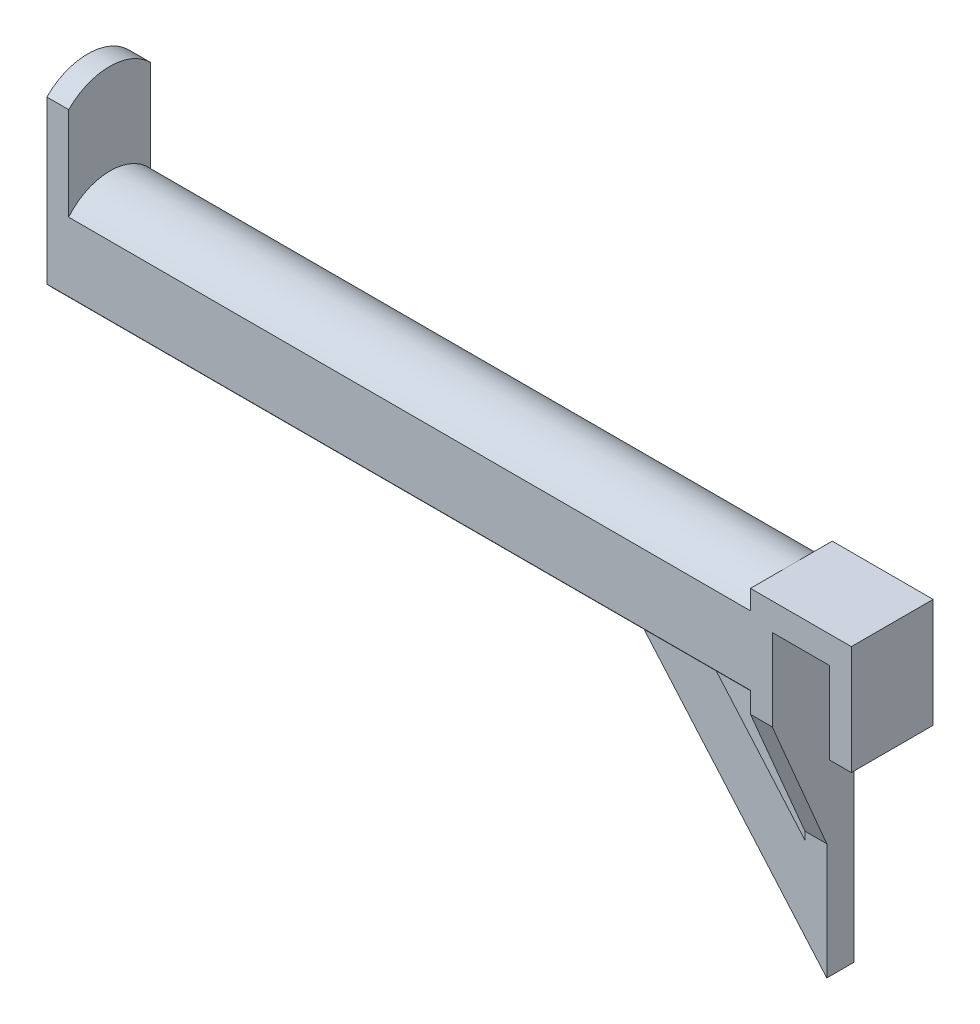
SolidWorks part; units mm, degrees
ref_plane "Front Plane" through (0, 0, 0) normal (0, 0, 1) x (1, 0, 0)
ref_plane "Top Plane" through (0, 0, 0) normal (0, 1, 0) x (1, 0, 0)
ref_plane "Right Plane" through (0, 0, 0) normal (1, 0, 0) x (0, 0, -1)
sketch "Sketch1" plane through (0, 0, 0) normal (0, 0, 1) x (1, 0, 0)
  line L0 (0, 0) -> (21, 0)
  line L1 (21, 0) -> (21, -30)
  line L2 (21, -30) -> (29, -30)
  line L3 (29, -30) -> (29, 10)
  line L4 (29, 10) -> (-8, 10)
  line L5 (-8, 10) -> (-8, -30)
  line L6 (-8, -30) -> (0, -30)
  line L7 (0, -30) -> (0, 0)
  line L8 (0, -30) -> (21, -30) construction
  dimension "D1" = 8
  dimension "D2" = 21
  dimension "D3" = 10
  dimension "D4" = 30
extrude "Boss-Extrude1" add sketch "Sketch1" along normal blind 30
sketch "Sketch2" plane through (-8, 0, 0) normal (-1, 0, 0) x (0, 0, 1)
  line L0 (0, 10) -> (30, -30) construction
  line L1 (0, -22.812) -> (0, 3.3137)
  line L2 (0, 10) -> (0, -30) construction
  line L3 (30, 2.8742) -> (30, -22.3725)
  line L4 (30, 10) -> (30, -30) construction
  arc A0 (0, -22.812) -> (30, -22.3725) centre (14.8119, -9.7491) ccw
  arc A1 (30, 2.8742) -> (0, 3.3137) centre (14.8119, -9.7491) ccw
extrude "Boss-Extrude2" add sketch "Sketch2" along normal blind 250
sketch "Sketch3" plane through (-258, 0, 0) normal (-1, 0, 0) x (0, 0, 1)
  line L0 (0, 37.0348) -> (30, 37.0348) construction
  line L2 (30, -22.3725) -> (30, 2.8742)
  line L3 (0, 3.3137) -> (0, -22.812)
  line L4 (30, -22.3725) -> (30, 37.0348)
  line L5 (0, 37.0348) -> (0, -22.812)
  arc A0 (0, 37.0348) -> (30, 37.0348) centre (15, 22.0348) cw
  arc A2 (0, -22.812) -> (30, -22.3725) centre (14.8119, -9.7491) ccw
  arc A3 (30, 2.8742) -> (0, 3.3137) centre (14.8119, -9.7491) ccw
  arc A4 (0, -22.812) -> (30, -22.3725) centre (14.8119, -9.7491) ccw
  point P9 (30, 19.8024)
  dimension "D1" = 0
extrude "Boss-Extrude3" add sketch "Sketch3" along normal blind 8
sketch "Sketch4" plane through (0, 0, 0) normal (0, 0, 1) x (1, 0, 0)
  line L0 (-84.4787, -22.3725) -> (0, -119.7384)
  line L1 (-266, -22.3725) -> (-8, -22.3725) construction
  line L2 (0, -119.7384) -> (0, -30)
  line L3 (0, -30) -> (-8, -30)
  line L4 (-8, -30) -> (-8, -80)
  line L5 (-8, -80) -> (-58, -22.3725)
  line L6 (-58, -22.3725) -> (-84.4787, -22.3725)
  dimension "D1" = 20
  dimension "D2" = 50
  dimension "D3" = 50
extrude "Boss-Extrude4" add sketch "Sketch4" along normal blind 10
chamfer "Chamfer1" distance 20 angle 67 1 edges at (-4, -30, 10) first distance on face at (-4, -30, 20)
